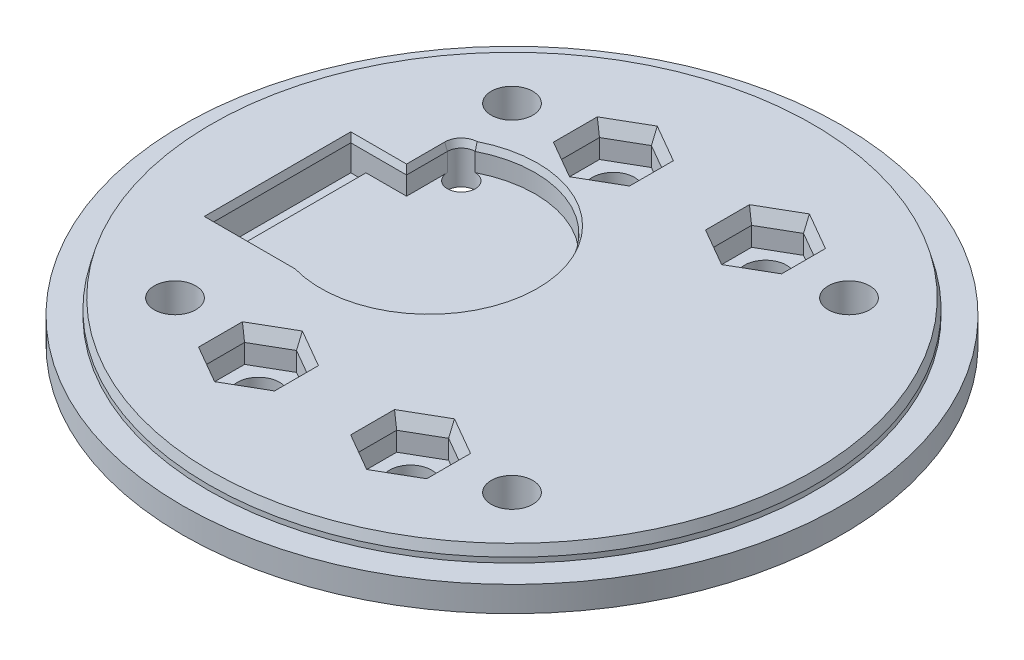
SolidWorks part; units mm, degrees
ref_plane "Спереди" through (0, 0, 0) normal (0, 0, 1) x (1, 0, 0)
ref_plane "Сверху" through (0, 0, 0) normal (0, 1, 0) x (1, 0, 0)
ref_plane "Справа" through (0, 0, 0) normal (1, 0, 0) x (0, 0, -1)
sketch "Эскиз1" plane through (0, 0, 0) normal (0, 1, 0) x (1, 0, 0)
  circle A0 centre (0, 0) radius 65
  dimension "D1" = 130
extrude "Бобышка-Вытянуть1" add sketch "Эскиз1" along normal blind 5
sketch "Эскиз2" plane through (0, 5, 0) normal (0, 1, 0) x (1, 0, 0)
  circle A0 centre (0, 0) radius 59.85
  dimension "D1" = 119.7
extrude "Бобышка-Вытянуть2" add sketch "Эскиз2" along normal blind 3
sketch "Эскиз3" plane through (0, 0, 0) normal (0, -1, 0) x (1, 0, 0)
  line L1 (25, -25) -> (-25, -25)
  line L2 (25, -25) -> (25, 25)
  line L3 (25, 25) -> (-25, 25)
  line L4 (-25, -25) -> (-25, 25)
  line L5 (25, -25) -> (-25, 25) construction
  line L6 (25, 25) -> (-25, -25) construction
  point P0 (0, 0)
  dimension "D1" = 50
  dimension "D2" = 50
extrude "Бобышка-Вытянуть3" add sketch "Эскиз3" along normal blind 25
sketch "Эскиз5" plane through (0, 0, 0) normal (0, -1, 0) x (1, 0, 0)
  line L1 (33.234, -33.234) -> (-33.234, -33.234) construction
  line L2 (33.234, -33.234) -> (33.234, 33.234) construction
  line L3 (33.234, 33.234) -> (-33.234, 33.234) construction
  line L4 (-33.234, -33.234) -> (-33.234, 33.234) construction
  line L5 (33.234, -33.234) -> (-33.234, 33.234) construction
  line L6 (33.234, 33.234) -> (-33.234, -33.234) construction
  circle A1 centre (33.234, -33.234) radius 4.1
  circle A2 centre (-33.234, -33.234) radius 4.1
  circle A3 centre (-33.234, 33.234) radius 4.1
  circle A4 centre (33.234, 33.234) radius 4.1
  circle A5 centre (0, 0) radius 47 construction
  point P0 (0, 0)
  dimension "D1" = 94
  dimension "D2" = 8.2
extrude "Вырез-Вытянуть2" cut sketch "Эскиз5" against normal through all
sketch "Эскиз6" plane through (0, 8, 0) normal (0, 1, 0) x (1, 0, 0)
  line L0 (0, 0) -> (0, 52.4) construction
  line L1 (0, 20) -> (-30, 20) construction
  circle A0 centre (0, 0) radius 59.85 construction
  circle A1 centre (-30, 20) radius 2.75
  dimension "D3" = 5.5
  dimension "D1" = 20
  dimension "D2" = 30
extrude "Вырез-Вытянуть3" cut sketch "Эскиз6" against normal through all
sketch "Sketch2" plane through (-25, 0, 0) normal (-1, 0, 0) x (0, 0, 1)
  line L0 (-25, -25) -> (25, 0) construction
  line L2 (10.125, -17.675) -> (-10.125, -17.675)
  line L3 (10.125, -17.675) -> (10.125, -7.325)
  line L4 (10.125, -7.325) -> (-10.125, -7.325)
  line L5 (-10.125, -17.675) -> (-10.125, -7.325)
  line L6 (10.125, -17.675) -> (-10.125, -7.325) construction
  line L7 (10.125, -7.325) -> (-10.125, -17.675) construction
  point P2 (0, -12.5)
  point P10 (0, -12.5)
  dimension "D1" = 20.25
  dimension "D2" = 10.35
extrude "Cut-Extrude1" cut sketch "Sketch2" against normal through all
chamfer "Chamfer1" distance 2 angle 15 1 edges at (0, 8, 59.85) first distance on face at (0, 8, 59.85)
sketch "Sketch4" plane through (0, -25, 0) normal (0, -1, 0) x (1, 0, 0)
  line L0 (-25, 0) -> (25, 0) construction
  line L1 (-25, 25) -> (-25, -25) construction
  line L2 (25, -25) -> (25, 25) construction
  line L4 (25, -25) -> (-25, -25)
  line L5 (25, -25) -> (25, 25)
  line L6 (25, 25) -> (-25, 25)
  line L7 (-25, -25) -> (-25, 25)
  line L8 (25, -25) -> (-25, 25) construction
  line L9 (25, 25) -> (-25, -25) construction
  point P6 (0, 0)
extrude "Cut-Extrude3" cut sketch "Sketch4" against normal blind 12.5
sketch "Sketch5" plane through (0, -7.325, 0) normal (0, -1, 0) x (1, 0, 0)
  line L0 (0, 10.125) -> (0, -10.125) construction
  line L1 (25, 10.125) -> (-25, 10.125) construction
  line L2 (25, -10.125) -> (-25, -10.125) construction
  line L4 (25, -45) -> (-25, -45)
  line L5 (25, -45) -> (25, 45)
  line L6 (25, 45) -> (-25, 45)
  line L7 (-25, -45) -> (-25, 45)
  line L8 (25, -45) -> (-25, 45) construction
  line L9 (25, 45) -> (-25, -45) construction
  point P6 (0, 0)
  dimension "D1" = 50
  dimension "D2" = 90
extrude "Boss-Extrude2" add sketch "Sketch5" against normal up to surface (7.325 mm away) from offset 2 up to face at (-30, 0, -17.25) offset against normal yes
sketch "Sketch6" plane through (0, -5.325, 0) normal (0, -1, 0) x (1, 0, 0)
  line L0 (25, 35) -> (-25, 35) construction
  line L1 (25, 25) -> (25, 45) construction
  line L2 (-25, 45) -> (-25, 25) construction
  line L3 (25, -35) -> (-25, -35) construction
  line L4 (25, -45) -> (25, -25) construction
  line L5 (-25, -25) -> (-25, -45) construction
  line L6 (0, 45) -> (0, -45) construction
  line L7 (25, 45) -> (-25, 45) construction
  line L8 (-25, -45) -> (25, -45) construction
  line L9 (-15, 35) -> (15, -35) construction
  line L10 (-15, -35) -> (15, 35) construction
  circle A0 centre (-15, 35) radius 4.15
  circle A1 centre (-15, -35) radius 4.15
  circle A2 centre (15, 35) radius 4.15
  circle A3 centre (15, -35) radius 4.15
  point P21 (0, 0)
  point P31 (0, 0)
  dimension "D3" = 8.3
  dimension "D1" = 10
  dimension "D2" = 10
  dimension "D4" = 30
  dimension "D5" = 70
  dimension "D6" = 70
extrude "Cut-Extrude4" cut sketch "Sketch6" against normal through all
sketch "Sketch7" plane through (0, 8, 0) normal (0, 1, 0) x (1, 0, 0)
  line L1 (-15, -42.5) -> (-8.5048, -38.75)
  line L2 (-8.5048, -38.75) -> (-8.5048, -31.25)
  line L3 (-8.5048, -31.25) -> (-15, -27.5)
  line L4 (-15, -27.5) -> (-21.4952, -31.25)
  line L5 (-21.4952, -31.25) -> (-21.4952, -38.75)
  line L6 (-21.4952, -38.75) -> (-15, -42.5)
  line L7 (-15, 27.5) -> (-8.5048, 31.25)
  line L8 (-8.5048, 31.25) -> (-8.5048, 38.75)
  line L9 (-8.5048, 38.75) -> (-15, 42.5)
  line L10 (-15, 42.5) -> (-21.4952, 38.75)
  line L11 (-21.4952, 38.75) -> (-21.4952, 31.25)
  line L12 (-21.4952, 31.25) -> (-15, 27.5)
  line L13 (15, -42.5) -> (21.4952, -38.75)
  line L14 (21.4952, -38.75) -> (21.4952, -31.25)
  line L15 (21.4952, -31.25) -> (15, -27.5)
  line L16 (15, -27.5) -> (8.5048, -31.25)
  line L17 (8.5048, -31.25) -> (8.5048, -38.75)
  line L18 (8.5048, -38.75) -> (15, -42.5)
  line L19 (15, 27.5) -> (21.4952, 31.25)
  line L20 (21.4952, 31.25) -> (21.4952, 38.75)
  line L21 (21.4952, 38.75) -> (15, 42.5)
  line L22 (15, 42.5) -> (8.5048, 38.75)
  line L23 (8.5048, 38.75) -> (8.5048, 31.25)
  line L24 (8.5048, 31.25) -> (15, 27.5)
  circle A0 centre (-15, -35) radius 7.5 construction
  circle A1 centre (-15, 35) radius 7.5 construction
  circle A2 centre (15, -35) radius 7.5 construction
  circle A3 centre (15, 35) radius 7.5 construction
  dimension "D1" = 15
extrude "Cut-Extrude5" cut sketch "Sketch7" against normal blind 6.5
chamfer "Chamfer2" distance 1 angle 70 24 edges at (-11.7524, 8, 29.375) (-8.5048, 8, 35) (-11.7524, 8, 40.625) (-18.2476, 8, 40.625) (-21.4952, 8, 35) (-18.2476, 8, 29.375) (-11.7524, 8, -29.375) (-8.5048, 8, -35) (-11.7524, 8, -40.625) (-18.2476, 8, -40.625) (-21.4952, 8, -35) (-18.2476, 8, -29.375) (11.7524, 8, -40.625) (18.2476, 8, -40.625) (21.4952, 8, -35) (18.2476, 8, -29.375) (11.7524, 8, -29.375) (8.5048, 8, -35) (11.7524, 8, 29.375) (18.2476, 8, 29.375) (21.4952, 8, 35) (18.2476, 8, 40.625) (11.7524, 8, 40.625) (8.5048, 8, 35) first distance on face at (-15, 8, -35)
sketch "Sketch8" plane through (0, 8, 0) normal (0, 1, 0) x (1, 0, 0)
  line L1 (-26.25, 11.95) -> (-43.75, 11.95)
  line L2 (-26.25, 11.95) -> (-26.25, -15.95)
  line L3 (-26.25, -15.95) -> (-43.75, -15.95)
  line L4 (-43.75, 11.95) -> (-43.75, -15.95)
  line L5 (-26.25, 11.95) -> (-43.75, -15.95) construction
  line L6 (-26.25, -15.95) -> (-43.75, 11.95) construction
  point P0 (-35, -2)
  dimension "D1" = 27.9
  dimension "D2" = 17.5
  dimension "D3" = 35
  dimension "D4" = 2
extrude "Cut-Extrude6" cut sketch "Sketch8" against normal blind 5
chamfer "Chamfer3" distance 10 angle 45 4 edges at (25, -2.6625, 45) (25, -2.6625, -45) (-25, -2.6625, -45) (-25, -2.6625, 45)
chamfer "Chamfer6" distance 3 angle 30 4 edges at (-25, -2.6625, -35) (-25, -2.6625, 35) (25, -2.6625, 35) (25, -2.6625, -35) first distance on face at (-20, -2.6625, -40) first distance on face at (-20, -2.6625, 40) first distance on face at (20, -2.6625, 40) first distance on face at (20, -2.6625, -40)
sketch "Sketch10" plane through (0, 8, 0) normal (0, 1, 0) x (1, 0, 0)
  line L0 (-32.75, 20) -> (-32.75, 11.95)
  line L1 (-26.25, 11.95) -> (-43.75, 11.95) construction
  line L2 (-32.75, 11.95) -> (-26.25, 11.95)
  line L3 (-26.25, 11.95) -> (-26.25, -15.95)
  circle A0 centre (-30, 20) radius 2.75 construction
  arc A1 (-26.25, -15.95) -> (-30, 22.75) centre (-20.4864, 4.1402) ccw
  arc A2 (-30, 22.75) -> (-32.75, 20) centre (-30, 20) ccw
extrude "Cut-Extrude8" cut sketch "Sketch10" against normal up to surface (5 mm away) up to face at (-35, 3, 2)
chamfer "Chamfer7" distance 0.5 angle 70 6 edges at (-31.9445, 8, -21.9445) (-32.75, 8, -15.975) (0.3167, 8, -6.156) (-38.25, 8, -11.95) (-43.75, 8, 2) (-35, 8, 15.95) first distance on face at (-30.2296, 8, -6.3459)
sketch "Sketch11" plane through (0, 3, 0) normal (0, 1, 0) x (1, 0, 0)
  line L0 (-42.25, -15.95) -> (-42.25, 11.95) construction
  line L1 (-43.75, -15.95) -> (-26.25, -15.95) construction
  line L2 (-32.75, 11.95) -> (-43.75, 11.95) construction
  line L4 (-40.75, 11.95) -> (-43.75, 11.95)
  line L5 (-40.75, 11.95) -> (-40.75, -15.95)
  line L6 (-40.75, -15.95) -> (-43.75, -15.95)
  line L7 (-43.75, 11.95) -> (-43.75, -15.95)
  line L8 (-40.75, 11.95) -> (-43.75, -15.95) construction
  line L9 (-40.75, -15.95) -> (-43.75, 11.95) construction
  point P6 (-42.25, -2)
  dimension "D1" = 3
extrude "Cut-Extrude9" cut sketch "Sketch11" against normal blind 1.5
